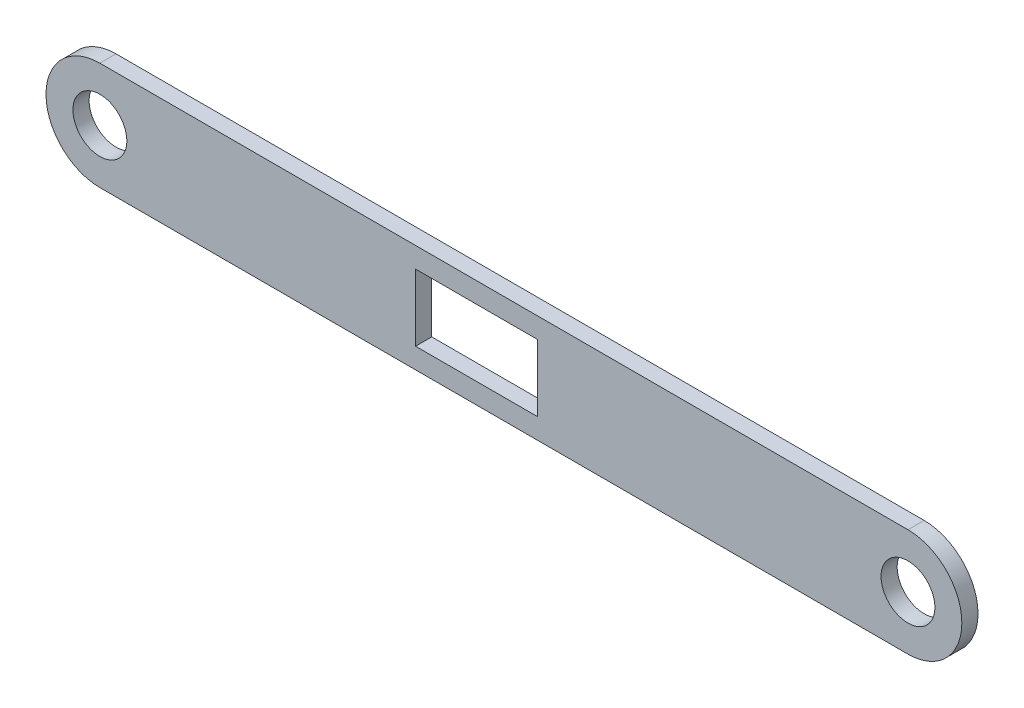
SolidWorks part; units mm, degrees
material "Acrylic (Medium-high impact)"
ref_plane "Front Plane" through (0, 0, 0) normal (0, 0, 1) x (1, 0, 0)
ref_plane "Top Plane" through (0, 0, 0) normal (0, 1, 0) x (1, 0, 0)
ref_plane "Right Plane" through (0, 0, 0) normal (1, 0, 0) x (0, 0, -1)
sketch "Sketch1" plane through (0, 0, 0) normal (0, 0, 1) x (1, 0, 0)
  line L0 (75, 0) -> (-75, 0) construction
  line L1 (75, -10) -> (-75, -10)
  line L2 (75, 10) -> (-75, 10)
  line L3 (0, 10) -> (0, -10) construction
  line L5 (-16.4, 6.2) -> (6.2, 6.2)
  line L6 (-16.4, 6.2) -> (-16.4, -6.2)
  line L7 (-16.4, -6.2) -> (6.2, -6.2)
  line L8 (6.2, 6.2) -> (6.2, -6.2)
  line L9 (-16.4, 6.2) -> (6.2, -6.2) construction
  line L10 (-16.4, -6.2) -> (6.2, 6.2) construction
  arc A0 (75, -10) -> (75, 10) centre (75, 0) ccw
  arc A1 (-75, 10) -> (-75, -10) centre (-75, 0) ccw
  circle A2 centre (75, 0) radius 5
  circle A3 centre (-75, 0) radius 5
  point P2 (0, 0)
  point P14 (-5.1, 0)
  point P21 (0, 0)
  dimension "D2" = 10
  dimension "D1" = 150
  dimension "D3" = 20
  dimension "D4" = 22.6
  dimension "D5" = 12.4
  dimension "D6" = 6.2
extrude "Boss-Extrude1" add sketch "Sketch1" along normal blind 3
